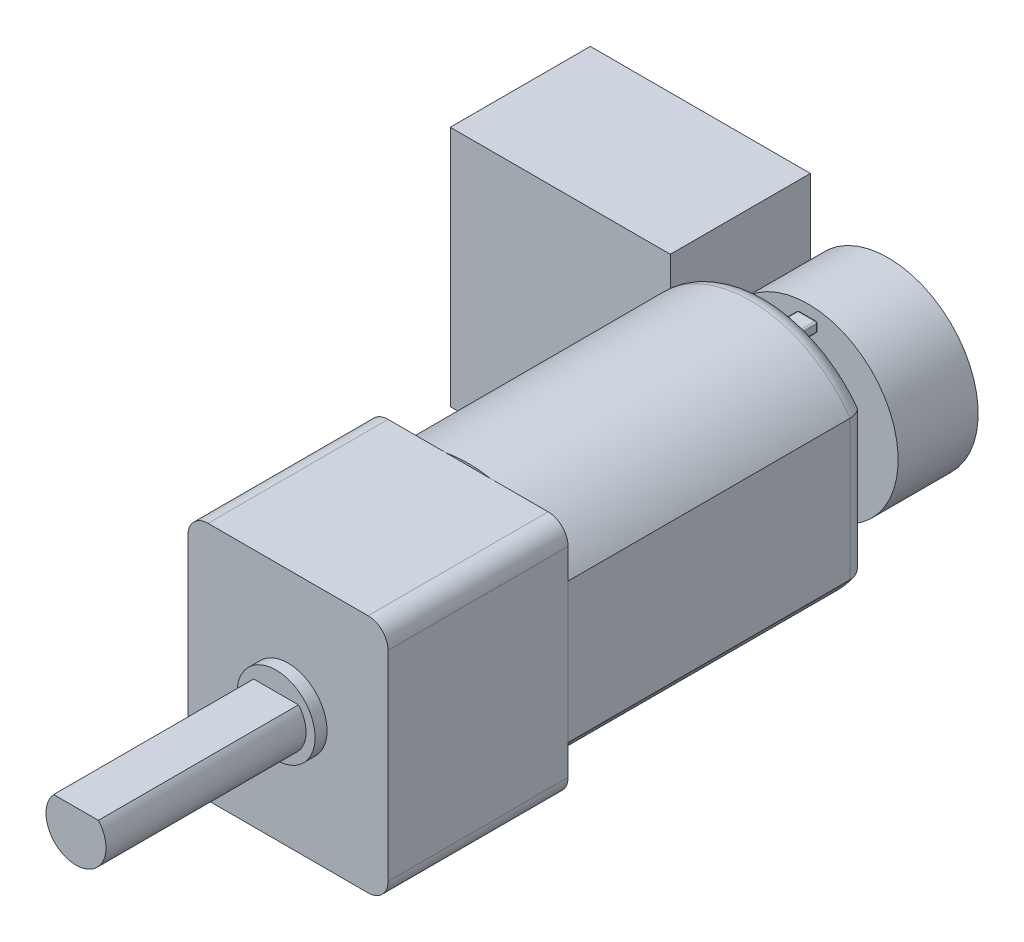
SolidWorks part; units mm, degrees
ref_plane "Alzado" through (0, 0, 0) normal (0, 0, 1) x (1, 0, 0)
ref_plane "Planta" through (0, 0, 0) normal (0, 1, 0) x (1, 0, 0)
ref_plane "Vista lateral" through (0, 0, 0) normal (1, 0, 0) x (0, 0, -1)
sketch "Croquis1" plane through (0, 0, 0) normal (0, 0, 1) x (1, 0, 0)
  line L1 (0, 0) -> (10, 0)
  line L2 (0, 0) -> (0, 12)
  line L3 (0, 12) -> (10, 12)
  line L4 (10, 0) -> (10, 12)
  dimension "D1" = 10
  dimension "D2" = 12
extrude "Saliente-Extruir1" add sketch "Croquis1" along normal blind 9
sketch "Croquis2" plane through (0, 0, 0) normal (0, 0, -1) x (-1, 0, 0)
  line L0 (-10, 9.5) -> (-10, 2.5)
  line L1 (-10, 0) -> (-10, 12) construction
  line L2 (-10, 12) -> (0, 12) construction
  line L3 (0, 0) -> (-10, 0) construction
  line L4 (0, 2.5) -> (0, 9.5)
  line L5 (0, 12) -> (0, 0) construction
  line L6 (-5, 12) -> (-5, 0) construction
  line L7 (-10, 6) -> (0, 6) construction
  arc A0 (-10, 9.5) -> (0, 9.5) centre (-5, 6) cw
  arc A1 (-10, 2.5) -> (0, 2.5) centre (-5, 6) ccw
extrude "Saliente-Extruir2" add sketch "Croquis2" along normal blind 15
sketch "Croquis3" plane through (0, 0, -15) normal (0, 0, -1) x (-1, 0, 0)
  line L1 (-5.5, 9.4983) -> (-4.5, 9.4983)
  line L2 (-5.5, 1.5203) -> (-4.5, 1.5203)
  line L3 (-5.5, 9.4983) -> (-5.5, 9.9983)
  line L4 (-5.5, 9.9983) -> (-4.5, 9.9983)
  line L5 (-4.5, 9.9983) -> (-4.5, 9.4983)
  line L6 (-5.5, 1.5203) -> (-5.5, 1.0203)
  line L7 (-5.5, 1.0203) -> (-4.5, 1.0203)
  line L8 (-4.5, 1.0203) -> (-4.5, 1.5203)
  dimension "D4" = 1
  dimension "D5" = 1
  dimension "D8" = 0.5
  dimension "D9" = 0.5
extrude "Saliente-Extruir3" add sketch "Croquis3" along normal blind 2
sketch "Croquis4" plane through (0, 0, -15) normal (0, 0, -1) x (-1, 0, 0)
  circle A0 centre (-5, 6) radius 2.5
  dimension "D1" = 5
extrude "Saliente-Extruir4" add sketch "Croquis4" along normal blind 2
sketch "Croquis5" plane through (0, 0, 9) normal (0, 0, 1) x (1, 0, 0)
  line L0 (5, 12) -> (5, 0) construction
  line L1 (10, 12) -> (0, 12) construction
  line L2 (0, 0) -> (10, 0) construction
  line L3 (0, 6) -> (10, 6) construction
  line L4 (0, 12) -> (0, 0) construction
  line L5 (10, 0) -> (10, 12) construction
  circle A0 centre (5, 6) radius 1.95
  dimension "D1" = 3.9
extrude "Saliente-Extruir5" add sketch "Croquis5" along normal blind 0.6
sketch "Croquis6" plane through (0, 0, 9.6) normal (0, 0, 1) x (1, 0, 0)
  line L1 (3.882, 7) -> (6.118, 7)
  arc A0 (3.882, 7) -> (6.118, 7) centre (5, 6) ccw
extrude "Saliente-Extruir9" add sketch "Croquis6" along normal blind 10 contours L1 A0 region at (5, 5.852, 9.6)
sketch "Croquis7" plane through (10, 0, 0) normal (1, 0, 0) x (0, 0, -1)
  line L1 (15, 9.5) -> (0, 9.5)
  line L2 (15, 9.5) -> (15, 2.5)
  line L3 (15, 2.5) -> (0, 2.5)
  line L4 (0, 9.5) -> (0, 2.5)
extrude "Cortar-Extruir1" cut sketch "Croquis7" against normal blind 0.01
sketch "Croquis8" plane through (0, 0, 0) normal (-1, 0, 0) x (0, 0, 1)
  line L1 (-15, 9.5) -> (0, 9.5)
  line L2 (-15, 9.5) -> (-15, 2.5)
  line L3 (-15, 2.5) -> (0, 2.5)
  line L4 (0, 9.5) -> (0, 2.5)
extrude "Cortar-Extruir2" cut sketch "Croquis8" against normal blind 0.01
fillet "Redondeo1" radius 0.9 2 edges at (0.01, 6, -15) (9.99, 6, -15)
fillet "Redondeo2" radius 0.9 2 edges at (5, 12.1033, -15) (5, -0.1033, -15)
fillet "Redondeo3" radius 0.5 1 edges at (2.5, 6, -17)
sketch "Croquis9" plane through (0, 0, -17) normal (0, 0, -1) x (-1, 0, 0)
  circle A0 centre (-5, 6) radius 0.4628
extrude "Saliente-Extruir7" add sketch "Croquis9" along normal blind 0.01
fillet "Redondeo4" radius 0.09 16 edges at (5.5, 1.2703, -17) (5.5, 9.7483, -17) (4.5, 9.4983, -16) (4.5, 1.0203, -16) (5.5, 9.4983, -16) (4.5, 9.9983, -16) (4.5, 1.5203, -16) (5, 1.0203, -17) (5, 1.5203, -17) (4.5, 1.2703, -17) (5.5, 1.0203, -16) (5.5, 1.5203, -16) (4.5, 9.7483, -17) (5, 9.4983, -17) (5, 9.9983, -17) (5.5, 9.9983, -16)
fillet "Redondeo6" radius 1 4 edges at (10, 12, 4.5) (10, 0, 4.5) (0, 0, 4.5) (0, 12, 4.5)
sketch "Sketch2" plane through (0, 0, -17) normal (0, 0, -1) x (-1, 0, 0)
  circle A0 centre (-5, 6) radius 4.5
  dimension "D1" = 9
extrude "Boss-Extrude1" add sketch "Sketch2" along normal blind 4
sketch "Sketch3" plane through (0.01, 0, 0) normal (-1, 0, 0) x (0, 0, 1)
  line L1 (-14.1, 12.1033) -> (-21.1, 12.1033)
  line L2 (-14.1, 12.1033) -> (-14.1, 0)
  line L3 (-14.1, 0) -> (-21.1, 0)
  line L4 (-21.1, 12.1033) -> (-21.1, 0)
  arc A0 (-14.1, 12.1033) -> (-15, 11.2033) centre (-14.1, 11.2033) ccw construction
  dimension "D1" = 7
extrude "Boss-Extrude3" add sketch "Sketch3" along normal blind 10 and the other way blind 1
